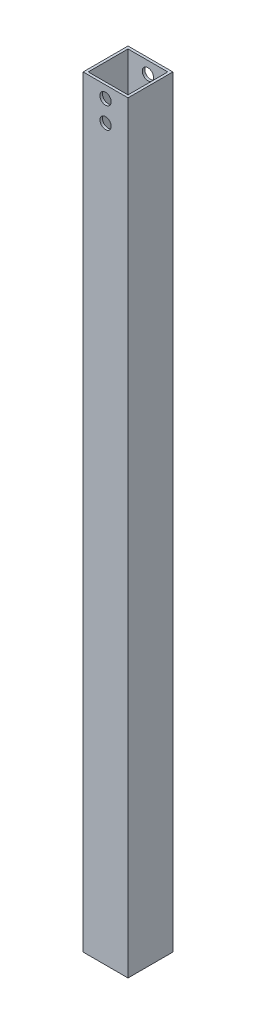
SolidWorks part; units mm, degrees
material "6061 Alloy"
ref_plane "Front Plane" through (0, 0, 0) normal (0, 0, 1) x (1, 0, 0)
ref_plane "Top Plane" through (0, 0, 0) normal (0, 1, 0) x (1, 0, 0)
ref_plane "Right Plane" through (0, 0, 0) normal (1, 0, 0) x (0, 0, -1)
sketch "Sketch1" plane through (0, 0, 0) normal (0, 1, 0) x (1, 0, 0)
  line L9 (12.7, -12.7) -> (-12.7, -12.7)
  line L10 (12.7, -12.7) -> (12.7, 12.7)
  line L11 (12.7, 12.7) -> (-12.7, 12.7)
  line L12 (-12.7, -12.7) -> (-12.7, 12.7)
  line L13 (12.7, -12.7) -> (-12.7, 12.7) construction
  line L14 (12.7, 12.7) -> (-12.7, -12.7) construction
  point P0 (0, 0)
  dimension "D1" = 25.4
extrude "Extrude-Thin1" add sketch "Sketch1" along normal blind 457.2 thin thin type mid plane wall 1.524
hole_wizard "1/4 Clearance Hole1" positions "Sketch2" profile "Sketch3" hole size "1/4" standard "ANSI Inch" end condition through all
sketch "Sketch2" plane through (0, 0, -13.462) normal (0, 0, -1) x (-1, 0, 0)
  point P0 (0, 450.0245)
  point P3 (0, 437.3245)
sketch "Sketch3" plane through (0, 450.0245, -13.462) normal (1, 0, 0) x (0, 1, 0)
  line L0 (0, 0) -> (0, 26.924)
  line L1 (0, 26.924) -> (3.3782, 26.924)
  line L2 (3.3782, 26.924) -> (3.3782, 0)
  line L5 (3.3782, 0) -> (0, 0)
  line L11 (0, -6.35) -> (0, 107.95) construction
  dimension "Thru Hole Dia." = 6.7564
  dimension "Thru Hole Depth" = 26.924
